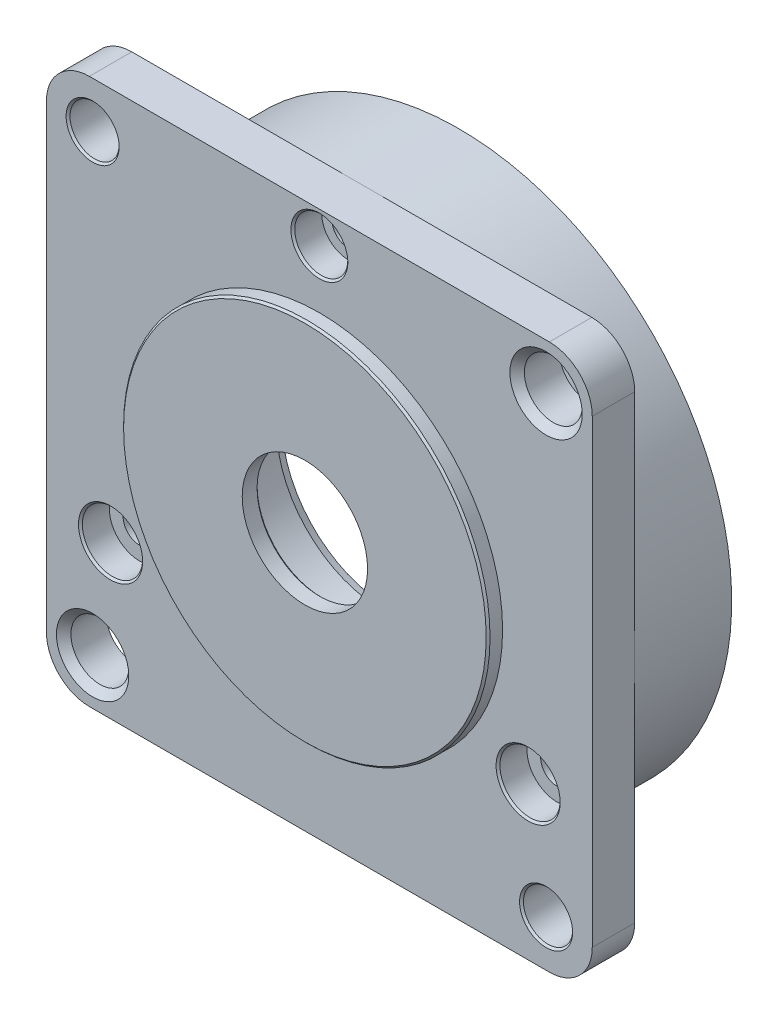
SolidWorks part; units mm, degrees
ref_plane "Ön Düzlem" through (0, 0, 0) normal (0, 0, 1) x (1, 0, 0)
ref_plane "Üst Düzlem" through (0, 0, 0) normal (0, 1, 0) x (1, 0, 0)
ref_plane "Sağ Düzlem" through (0, 0, 0) normal (1, 0, 0) x (0, 0, -1)
sketch "Çizim1" plane through (0, 0, 0) normal (0, 0, 1) x (1, 0, 0)
  line L1 (-23.85, 28.3) -> (23.85, 28.3)
  line L2 (-28.3, 23.85) -> (-28.3, -23.85)
  line L3 (-23.85, -28.3) -> (23.85, -28.3)
  line L4 (28.3, 23.85) -> (28.3, -23.85)
  line L5 (-28.3, 28.3) -> (28.3, -28.3) construction
  line L6 (-28.3, -28.3) -> (28.3, 28.3) construction
  arc A0 (23.85, 28.3) -> (28.3, 23.85) centre (23.85, 23.85) cw
  arc A1 (-23.85, 28.3) -> (-28.3, 23.85) centre (-23.85, 23.85) ccw
  arc A2 (-28.3, -23.85) -> (-23.85, -28.3) centre (-23.85, -23.85) ccw
  arc A3 (23.85, -28.3) -> (28.3, -23.85) centre (23.85, -23.85) ccw
  circle A4 centre (-23.5113, 23.5113) radius 2.55
  circle A5 centre (23.5113, -23.5113) radius 2.55
  circle A6 centre (-23.5113, -23.5113) radius 3
  circle A7 centre (23.5113, 23.5113) radius 3
  circle A8 centre (0, 0) radius 6.5
  circle A9 centre (0, 25) radius 1.7
  circle A10 centre (21.6506, -12.5) radius 1.7
  circle A11 centre (-21.6506, -12.5) radius 1.7
  point P0 (0, 0)
  point P38 (0, 0)
  dimension "D3" = 4.45
  dimension "D4" = 5.1
  dimension "D5" = 5.1
  dimension "D8" = 66.5
  dimension "D10" = 6
  dimension "D11" = 6
  dimension "D12" = 13
  dimension "D13" = 3.4
  dimension "D1" = 56.6
  dimension "D2" = 56.6
  dimension "D6" = 66.5
  dimension "D7" = 33.25
  dimension "D9" = 33.25
  dimension "D14" = 25
  dimension "D15" = 3
extrude "Yükseklik-Ekstrüzyon1" add sketch "Çizim1" along normal blind 4.4
sketch "Çizim2" plane through (0, 0, 4.4) normal (0, 0, 1) x (1, 0, 0)
  circle A0 centre (0, 0) radius 6.5 construction
  circle A1 centre (0, 0) radius 6.5
  circle A2 centre (0, 0) radius 19
  dimension "D1" = 38
extrude "Yükseklik-Ekstrüzyon2" add sketch "Çizim2" along normal blind 1.5
chamfer "Pah1" distance 0.2 angle 45 1 edges at (19, 0, 5.9)
chamfer "Pah2" distance 0.75 angle 45 2 edges at (26.5113, 23.5113, 4.4) (-20.5113, -23.5113, 4.4)
sketch "Çizim3" plane through (0, 0, 4.4) normal (0, 0, 1) x (1, 0, 0)
  circle A0 centre (-21.6506, -12.5) radius 3.125
  circle A1 centre (21.6506, -12.5) radius 3.125
  circle A2 centre (0, 25) radius 2.75
  circle A3 centre (0, 25) radius 1.7 construction
  circle A4 centre (21.6506, -12.5) radius 1.7 construction
  circle A5 centre (-21.6506, -12.5) radius 1.7 construction
  circle A6 centre (0, 25) radius 1.7
  circle A7 centre (21.6506, -12.5) radius 1.7
  circle A8 centre (-21.6506, -12.5) radius 1.7
  dimension "D1" = 6.25
  dimension "D2" = 5.5
extrude "Kes-Ekstrüzyon1" cut sketch "Çizim3" against normal blind 3
chamfer "Pah3" distance 0.2 angle 45 5 edges at (26.0613, -23.5113, 4.4) (-20.9613, 23.5113, 4.4) (2.75, 25, 4.4) (-18.5256, -12.5, 4.4) (24.7756, -12.5, 4.4)
sketch "Çizim4" plane through (0, 0, 0) normal (0, 0, -1) x (-1, 0, 0)
  circle A0 centre (0, 0) radius 11
  dimension "D1" = 22
extrude "Kes-Ekstrüzyon2" cut sketch "Çizim4" against normal blind 3.66
sketch "Çizim5" plane through (0, 0, 3.66) normal (0, 0, -1) x (-1, 0, 0)
  circle A0 centre (0, 0) radius 8.9
  dimension "D1" = 17.8
extrude "Kes-Ekstrüzyon3" cut sketch "Çizim5" against normal blind 0.5
chamfer "Pah4" distance 0.2 angle 45 1 edges at (-6.5, 0, 4.16)
sketch "Çizim6" plane through (0, 0, 0) normal (0, 0, -1) x (-1, 0, 0)
  circle A0 centre (0, 0) radius 12.75
  circle A1 centre (0, 0) radius 11 construction
  circle A2 centre (0, 0) radius 11
  dimension "D1" = 25.5
extrude "Yükseklik-Ekstrüzyon3" add sketch "Çizim6" along normal blind 2.9
chamfer "Pah5" distance 0.2 angle 75 1 edges at (-11, 0, -2.9) first distance on face at (-12.75, 0, -2.9)
sketch "Çizim7" plane through (0, 0, 0) normal (0, 0, -1) x (-1, 0, 0)
  circle A0 centre (0, 0) radius 26.75
  circle A1 centre (0, 0) radius 28.3
  dimension "D1" = 53.5
  dimension "D2" = 56.6
extrude "Yükseklik-Ekstrüzyon4" add sketch "Çizim7" along normal blind 10.06
sketch "Çizim8" plane through (0, 0, 0) normal (0, 0, -1) x (-1, 0, 0)
  line L0 (-2.9, 25) -> (-2.9, 26.5923)
  line L1 (2.9, 25) -> (2.9, 26.5923)
  line L2 (23.1006, -9.9885) -> (24.4796, -10.7847)
  line L3 (20.2006, -15.0115) -> (21.5796, -15.8076)
  line L4 (-20.2006, -15.0115) -> (-21.5796, -15.8076)
  line L5 (-23.1006, -9.9885) -> (-24.4796, -10.7847)
  circle A0 centre (0, 0) radius 12.75 construction
  circle A1 centre (0, 0) radius 26.75 construction
  circle A2 centre (0, 0) radius 12.75
  arc A3 (-2.9, 26.5923) -> (-24.4796, -10.7847) centre (0, 0) ccw
  arc A4 (-2.9, 25) -> (2.9, 25) centre (0, 25) ccw
  arc A6 (23.1006, -9.9885) -> (20.2006, -15.0115) centre (21.6506, -12.5) ccw
  arc A7 (-20.2006, -15.0115) -> (-23.1006, -9.9885) centre (-21.6506, -12.5) ccw
  arc A8 (-21.5796, -15.8076) -> (21.5796, -15.8076) centre (0, 0) ccw
  arc A9 (24.4796, -10.7847) -> (2.9, 26.5923) centre (0, 0) ccw
  point P24 (0, 0)
  dimension "D1" = 5.8
  dimension "D2" = 3
extrude "Kes-Ekstrüzyon4" cut sketch "Çizim8" against normal blind 0.5
sketch "Çizim10" plane through (0, 0, -10.06) normal (0, 0, -1) x (-1, 0, 0)
  circle A0 centre (0, 0) radius 27.5
  dimension "D1" = 55
extrude "Kes-Ekstrüzyon5" cut sketch "Çizim10" against normal blind 1.5
